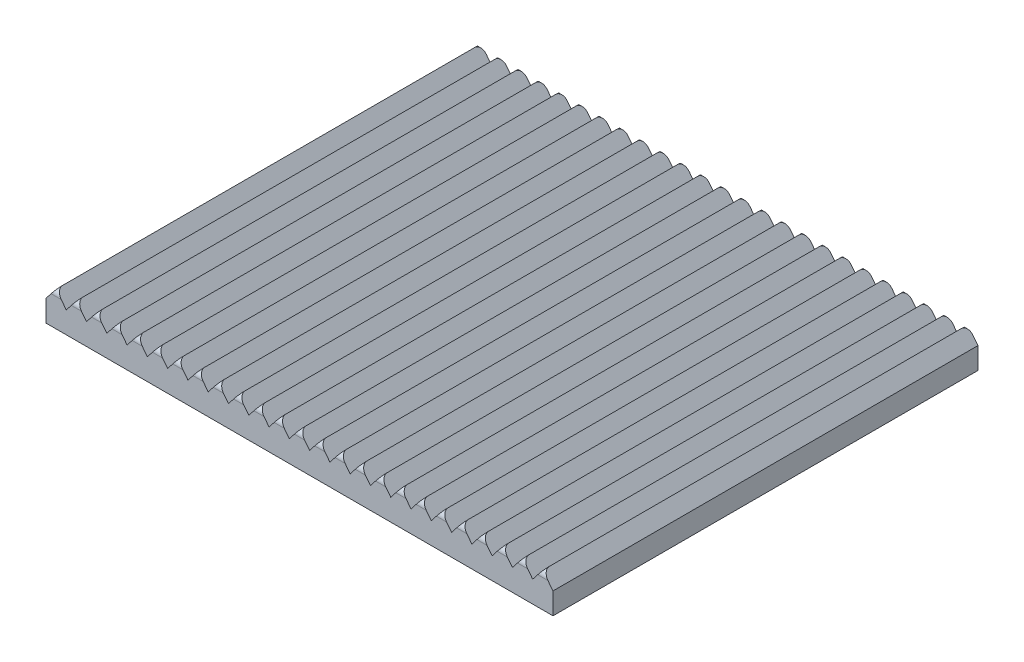
SolidWorks part; units mm, degrees
ref_plane "Front Plane" through (0, 0, 0) normal (0, 0, 1) x (1, 0, 0)
ref_plane "Top Plane" through (0, 0, 0) normal (0, 1, 0) x (1, 0, 0)
ref_plane "Right Plane" through (0, 0, 0) normal (1, 0, 0) x (0, 0, -1)
sketch "Sketch1" plane through (0, 0, 0) normal (0, 1, 0) x (1, 0, 0)
  line L6 (-29.375, 24.625) -> (29.375, 24.625)
  line L28 (-29.375, 24.625) -> (-29.375, -24.625)
  line L29 (-29.375, -24.625) -> (29.375, -24.625)
  line L30 (29.375, 24.625) -> (29.375, -24.625)
  line L31 (-29.375, 24.625) -> (29.375, -24.625) construction
  line L32 (-29.375, -24.625) -> (29.375, 24.625) construction
  circle A1 centre (0, 0) radius 3.05
  point P0 (0, 0)
  dimension "D3" = 6.1
  dimension "D1" = 58.75
  dimension "D2" = 49.25
extrude "Boss-Extrude1" add sketch "Sketch1" along normal blind 1.5
sketch "Sketch2" plane through (0, 0, -24.625) normal (0, 0, -1) x (-1, 0, 0)
  line L0 (-29.375, 1.5) -> (-29.375, 0) construction
  line L1 (-29.375, 1.5) -> (29.375, 1.5)
  line L2 (-29.375, 1.5) -> (-29.375, 2.5)
  line L4 (29.375, 1.5) -> (29.375, 2.5)
  line L5 (-1.175, 2.5) -> (0, 4)
  line L6 (0, 55) -> (0, -55) construction
  line L7 (1.175, 2.5) -> (0, 4)
  line L8 (1.175, 2.5) -> (2.35, 4)
  line L9 (3.525, 2.5) -> (2.35, 4)
  line L10 (3.525, 2.5) -> (4.7, 4)
  line L11 (5.875, 2.5) -> (4.7, 4)
  line L12 (5.875, 2.5) -> (7.05, 4)
  line L13 (8.225, 2.5) -> (7.05, 4)
  line L14 (8.225, 2.5) -> (9.4, 4)
  line L15 (10.575, 2.5) -> (9.4, 4)
  line L16 (10.575, 2.5) -> (11.75, 4)
  line L17 (12.925, 2.5) -> (11.75, 4)
  line L18 (12.925, 2.5) -> (14.1, 4)
  line L19 (15.275, 2.5) -> (14.1, 4)
  line L20 (15.275, 2.5) -> (16.45, 4)
  line L21 (17.625, 2.5) -> (16.45, 4)
  line L22 (17.625, 2.5) -> (18.8, 4)
  line L23 (19.975, 2.5) -> (18.8, 4)
  line L24 (19.975, 2.5) -> (21.15, 4)
  line L25 (22.325, 2.5) -> (21.15, 4)
  line L26 (22.325, 2.5) -> (23.5, 4)
  line L27 (24.675, 2.5) -> (23.5, 4)
  line L28 (24.675, 2.5) -> (25.85, 4)
  line L29 (27.025, 2.5) -> (25.85, 4)
  line L30 (27.025, 2.5) -> (28.2, 4)
  line L31 (29.375, 2.5) -> (28.2, 4)
  line L32 (-29.375, 2.5) -> (-28.2, 4)
  line L33 (-27.025, 2.5) -> (-28.2, 4)
  line L34 (-27.025, 2.5) -> (-25.85, 4)
  line L35 (-24.675, 2.5) -> (-25.85, 4)
  line L36 (-24.675, 2.5) -> (-23.5, 4)
  line L37 (-22.325, 2.5) -> (-23.5, 4)
  line L38 (-22.325, 2.5) -> (-21.15, 4)
  line L39 (-19.975, 2.5) -> (-21.15, 4)
  line L40 (-19.975, 2.5) -> (-18.8, 4)
  line L41 (-17.625, 2.5) -> (-18.8, 4)
  line L42 (-17.625, 2.5) -> (-16.45, 4)
  line L43 (-15.275, 2.5) -> (-16.45, 4)
  line L44 (-15.275, 2.5) -> (-14.1, 4)
  line L45 (-12.925, 2.5) -> (-14.1, 4)
  line L46 (-12.925, 2.5) -> (-11.75, 4)
  line L47 (-10.575, 2.5) -> (-11.75, 4)
  line L48 (-10.575, 2.5) -> (-9.4, 4)
  line L49 (-8.225, 2.5) -> (-9.4, 4)
  line L50 (-8.225, 2.5) -> (-7.05, 4)
  line L51 (-5.875, 2.5) -> (-7.05, 4)
  line L52 (-5.875, 2.5) -> (-4.7, 4)
  line L53 (-3.525, 2.5) -> (-4.7, 4)
  line L54 (-3.525, 2.5) -> (-2.35, 4)
  line L55 (-1.175, 2.5) -> (-2.35, 4)
  dimension "D1" = 1
  dimension "D2" = 1.5
  dimension "D3" = 13
extrude "Boss-Extrude2" add sketch "Sketch2" against normal up to surface (49.25 mm away) up to face at (0, 0.75, 24.625)
sketch "Sketch3" plane through (0, 0, 0) normal (0, -1, 0) x (-1, 0, 0)
  line L0 (0, 55) -> (0, -55) construction
  line L2 (-1.75, -2.498) -> (-1.75, -5)
  line L3 (-1.75, -5) -> (1.75, -5)
  line L4 (1.75, -2.498) -> (1.75, -5)
  arc A0 (1.75, -2.498) -> (-1.75, -2.498) centre (0, 0) ccw
  dimension "D2" = 6.1
  dimension "D1" = 3.5
  dimension "D3" = 5
  dimension "D4" = 1.75
extrude "Cut-Extrude1" cut sketch "Sketch3" against normal blind 2
sketch "Sketch4" plane through (29.375, 0, 0) normal (1, 0, 0) x (0, 0, -1)
  line L1 (-24.625, 4) -> (-24.625, 2.5) construction
  line L2 (-24.625, 4) -> (24.625, 4) construction
  line L3 (-23.875, 4) -> (-24.625, 4)
  line L4 (-24.625, 4) -> (-24.625, 3.25)
  arc A0 (-24.625, 3.25) -> (-23.875, 4) centre (-23.875, 3.25) cw
extrude "Cut-Extrude3" cut sketch "Sketch4" against normal through all
mirror "Mirror1" about plane through (0, 0, 0) normal (0, 0, 1) of "Cut-Extrude3"
chamfer "Chamfer3" distance 2 angle 45 1 edges at (0, 0, 5)
